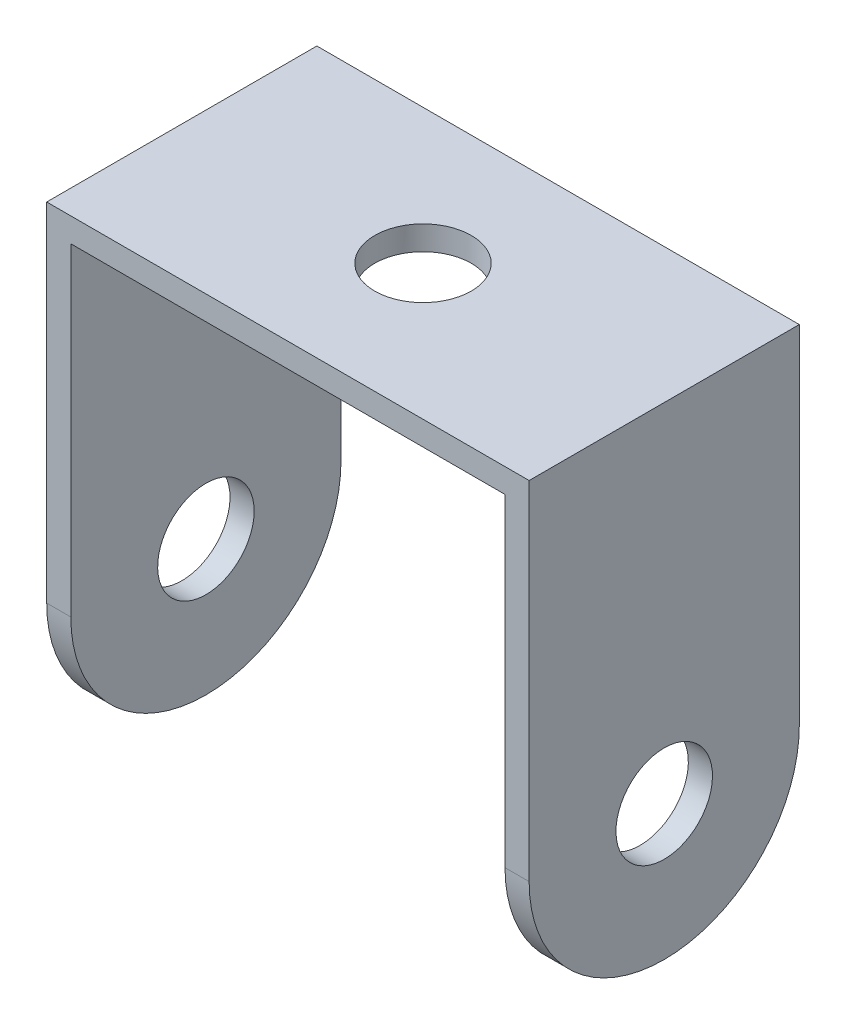
SolidWorks part; units mm, degrees
ref_plane "Plano frontal" through (0, 0, 0) normal (0, 0, 1) x (1, 0, 0)
ref_plane "Plano superior" through (0, 0, 0) normal (0, 1, 0) x (1, 0, 0)
ref_plane "Plano direito" through (0, 0, 0) normal (1, 0, 0) x (0, 0, -1)
sketch "Esboço1" plane through (0, 0, 0) normal (0, 0, 1) x (1, 0, 0)
  line L1 (-25, 25) -> (25, 25)
  line L2 (-25, 25) -> (-25, -25)
  line L3 (-25, -25) -> (25, -25)
  line L4 (25, 25) -> (25, -25)
  line L5 (-25, 25) -> (25, -25) construction
  line L6 (-25, -25) -> (25, 25) construction
  point P0 (0, 0)
  dimension "D1" = 50
  dimension "D2" = 50
extrude "Ressalto-extrusão1" add sketch "Esboço1" along normal blind 28
sketch "Esboço2" plane through (0, 0, 0) normal (0, 0, -1) x (-1, 0, 0)
  line L0 (-22.5, -25) -> (-22.5, 22.5)
  line L2 (-25, -25) -> (-25, 25)
  line L3 (-25, 25) -> (25, 25)
  line L4 (25, 25) -> (25, -25)
  line L5 (-22.5, 22.5) -> (22.5, 22.5)
  line L6 (22.5, 22.5) -> (22.5, -25)
  line L7 (-22.5, -25) -> (22.5, -25)
  line M5 (-25, -25) -> (25, -25)
  dimension "D1" = 2.5
extrude "Corte-extrusão1" cut sketch "Esboço2" against normal blind 28 contours L6 L5 L0 M5 region at (0, -1.25, 0)
sketch "Esboço3" plane through (0, 25, 0) normal (0, 1, 0) x (1, 0, 0)
  line L0 (25, -28) -> (-25, -28) construction
  line L2 (-25, -28) -> (-25, 0) construction
  circle A0 centre (0, -14) radius 5
  point P3 (0, -28)
  dimension "D1" = 10
  dimension "D2" = 14
  dimension "D3" = 25
extrude "Corte-extrusão2" cut sketch "Esboço3" against normal through all
sketch "Esboço4" plane through (25, 0, 0) normal (1, 0, 0) x (0, 0, -1)
  line L3 (-28, -25) -> (0, -25) construction
  line L5 (-28, -25) -> (-28, 25) construction
  circle A1 centre (-14, -11) radius 5
  dimension "D2" = 14
  dimension "D1" = 14
  dimension "D3" = 10
extrude "Corte-extrusão3" cut sketch "Esboço4" against normal through all
fillet "Filete1" radius 14 4 edges at (23.75, -25, 28) (-23.75, -25, 28) (-23.75, -25, 0) (23.75, -25, 0)
